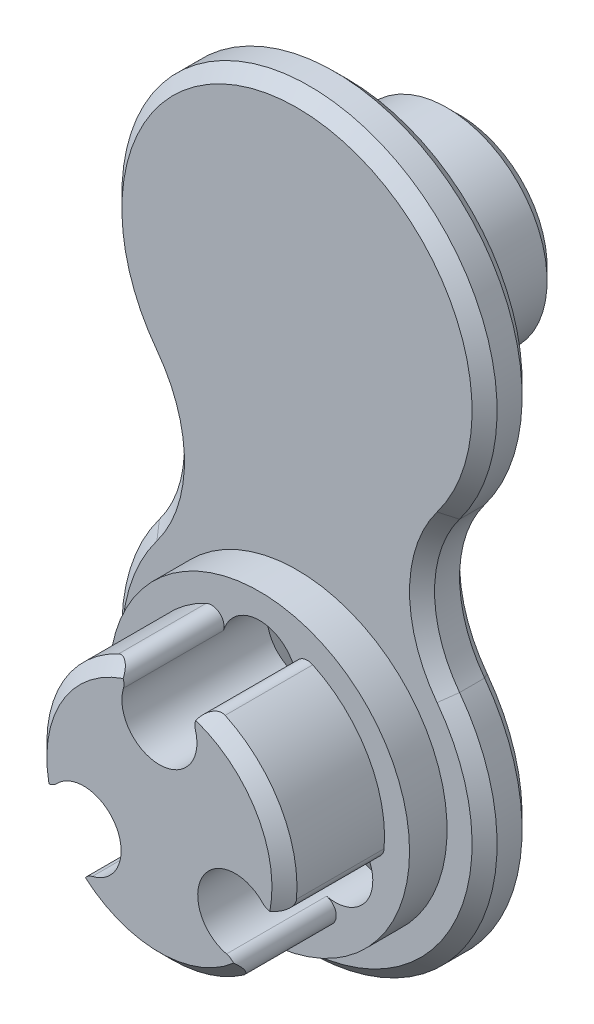
SolidWorks part; units mm, degrees
material "A2017"
ref_plane "正面" through (0, 0, 0) normal (0, 0, 1) x (1, 0, 0)
ref_plane "平面" through (0, 0, 0) normal (0, 1, 0) x (1, 0, 0)
ref_plane "右側面" through (0, 0, 0) normal (1, 0, 0) x (0, 0, -1)
sketch "ｽｹｯﾁ1" plane through (0, 0, 0) normal (0, 0, 1) x (1, 0, 0)
  line L0 (-5, 7.5) -> (5, 7.5) construction
  line L1 (0, 15) -> (0, 0) construction
  arc A0 (-6, 4.5) -> (6, 4.5) centre (0, 0) ccw
  arc A1 (6, 10.5) -> (-6, 10.5) centre (0, 15) ccw
  arc A2 (-6, 10.5) -> (-6, 4.5) centre (-10, 7.5) cw
  arc A3 (6, 10.5) -> (6, 4.5) centre (10, 7.5) ccw
  dimension "D1" = 15
  dimension "D2" = 15
  dimension "D3" = 10
extrude "ﾎﾞｽ - 押し出し1" add sketch "ｽｹｯﾁ1" along normal blind 2
sketch "ｽｹｯﾁ2" plane through (0, 0, 2) normal (0, 0, 1) x (1, 0, 0)
  circle A0 centre (0, 0) radius 6
  dimension "D1" = 12
extrude "ﾎﾞｽ - 押し出し2" add sketch "ｽｹｯﾁ2" along normal blind 1.5
sketch "ｽｹｯﾁ3" plane through (0, 0, 3.5) normal (0, 0, 1) x (1, 0, 0)
  circle A0 centre (0, 0) radius 5
  dimension "D1" = 10
extrude "ﾎﾞｽ - 押し出し3" add sketch "ｽｹｯﾁ3" along normal blind 4
sketch "ｽｹｯﾁ4" plane through (0, 0, 0) normal (0, 0, -1) x (-1, 0, 0)
  circle A0 centre (0, 15) radius 5
  dimension "D1" = 10
extrude "ﾎﾞｽ - 押し出し4" add sketch "ｽｹｯﾁ4" along normal blind 1
sketch "ｽｹｯﾁ5" plane through (0, 0, -1) normal (0, 0, -1) x (-1, 0, 0)
  circle A0 centre (0, 15) radius 4
  dimension "D1" = 8
extrude "ﾎﾞｽ - 押し出し5" add sketch "ｽｹｯﾁ5" along normal blind 3.5
hole_wizard "M4x0.7 ねじ穴1" [suppressed] positions "ｽｹｯﾁ7" profile "ｽｹｯﾁ6" tap size "M4x0.7" standard "Jis"
sketch "ｽｹｯﾁ7" plane through (0, 0, -6) normal (0, 0, -1) x (-1, 0, 0)
  point P0 (0, 15)
sketch "ｽｹｯﾁ6" plane through (0, 15, -6) normal (1, 0, 0) x (0, 1, 0)
  line L0 (0, 0) -> (0, 15)
  line L1 (0, 15) -> (1.65, 15)
  line L2 (1.65, 15) -> (1.65, 0)
  line L5 (1.65, 0) -> (0, 0)
  line L11 (0, -6.35) -> (0, 107.95) construction
  dimension "次ｻｰﾌｪｽまでのねじ下穴ﾄﾞﾘﾙ直径" = 3.3
  dimension "次ｻｰﾌｪｽまでのねじ下穴ﾄﾞﾘﾙの深さ" = 15
cosmetic thread "穴のねじ山1" [suppressed] parameters "D2"=4
sketch "ｽｹｯﾁ8" plane through (0, 0, 7.5) normal (0, 0, 1) x (1, 0, 0)
  line L0 (0, 3.5) -> (0, 0) construction
  line L1 (3.0311, -1.75) -> (0, 0) construction
  line L2 (-3.0311, -1.75) -> (0, 0) construction
  arc A0 (-1.4375, 3.9286) -> (1.4375, 3.9286) centre (0, 3.5) ccw
  circle A1 centre (0, 0) radius 5 construction
  arc A2 (-1.4375, 3.9286) -> (-2.1296, 4.5238) centre (-1.9166, 4.0714) ccw
  arc A3 (2.1296, 4.5238) -> (-2.1296, 4.5238) centre (0, 0) ccw
  arc A4 (1.4375, 3.9286) -> (2.1296, 4.5238) centre (1.9166, 4.0714) cw
  arc A5 (4.121, -0.7194) -> (2.6835, -3.2092) centre (3.0311, -1.75) ccw
  arc A6 (4.121, -0.7194) -> (4.9825, -0.4176) centre (4.4843, -0.3759) ccw
  arc A7 (2.8529, -4.1062) -> (4.9825, -0.4176) centre (0, 0) ccw
  arc A8 (2.6835, -3.2092) -> (2.8529, -4.1062) centre (2.5676, -3.6956) cw
  arc A9 (-2.6835, -3.2092) -> (-4.121, -0.7194) centre (-3.0311, -1.75) ccw
  arc A10 (-2.6835, -3.2092) -> (-2.8529, -4.1062) centre (-2.5676, -3.6956) ccw
  arc A11 (-4.9825, -0.4176) -> (-2.8529, -4.1062) centre (0, 0) ccw
  arc A12 (-4.121, -0.7194) -> (-4.9825, -0.4176) centre (-4.4843, -0.3759) cw
  point P26 (0, 0)
  dimension "D1" = 3
  dimension "D2" = 1
  dimension "D3" = 3
extrude "ｶｯﾄ - 押し出し1" cut sketch "ｽｹｯﾁ8" against normal through all
sketch "ｽｹｯﾁ9" plane through (0, 0, 3.5) normal (0, 0, 1) x (1, 0, 0)
  circle A0 centre (0, 0) radius 6 construction
  circle A1 centre (0, 0) radius 6
extrude "ﾎﾞｽ - 押し出し6" add sketch "ｽｹｯﾁ9" against normal up to surface (3.5 mm away) up to face at (-3.4427, -1.9876, 0)
sketch "ｽｹｯﾁ10" plane through (0, 0, 3.5) normal (0, 0, 1) x (1, 0, 0)
  arc A0 (-1.4375, 3.9286) -> (1.4375, 3.9286) centre (0, 3.5) ccw construction
  arc A1 (-2.6835, -3.2092) -> (-4.121, -0.7194) centre (-3.0311, -1.75) ccw construction
  arc A2 (4.121, -0.7194) -> (2.6835, -3.2092) centre (3.0311, -1.75) ccw construction
  circle A3 centre (0, 3.5) radius 1.5
  circle A4 centre (-3.0311, -1.75) radius 1.5
  circle A5 centre (3.0311, -1.75) radius 1.5
extrude "ｶｯﾄ - 押し出し2" cut sketch "ｽｹｯﾁ10" against normal through all
chamfer "面取り1" distance 1.7 angle 45 3 edges at (-4.5311, -1.75, 0) (-1.5, 3.5, 0) (1.5311, -1.75, 0)
chamfer "面取り2" distance 0.5 angle 45 5 edges at (-4, 15, -4.5) (0, 22.5, 0) (5, 7.5, 0) (0, -7.5, 0) (-5, 7.5, 0)
chamfer "面取り3" distance 0.5 angle 45 5 edges at (-4.3301, 2.5, 7.5) (0, -5, 7.5) (4.3301, 2.5, 7.5) (0, -7.5, 2) (0, 22.5, 2)
